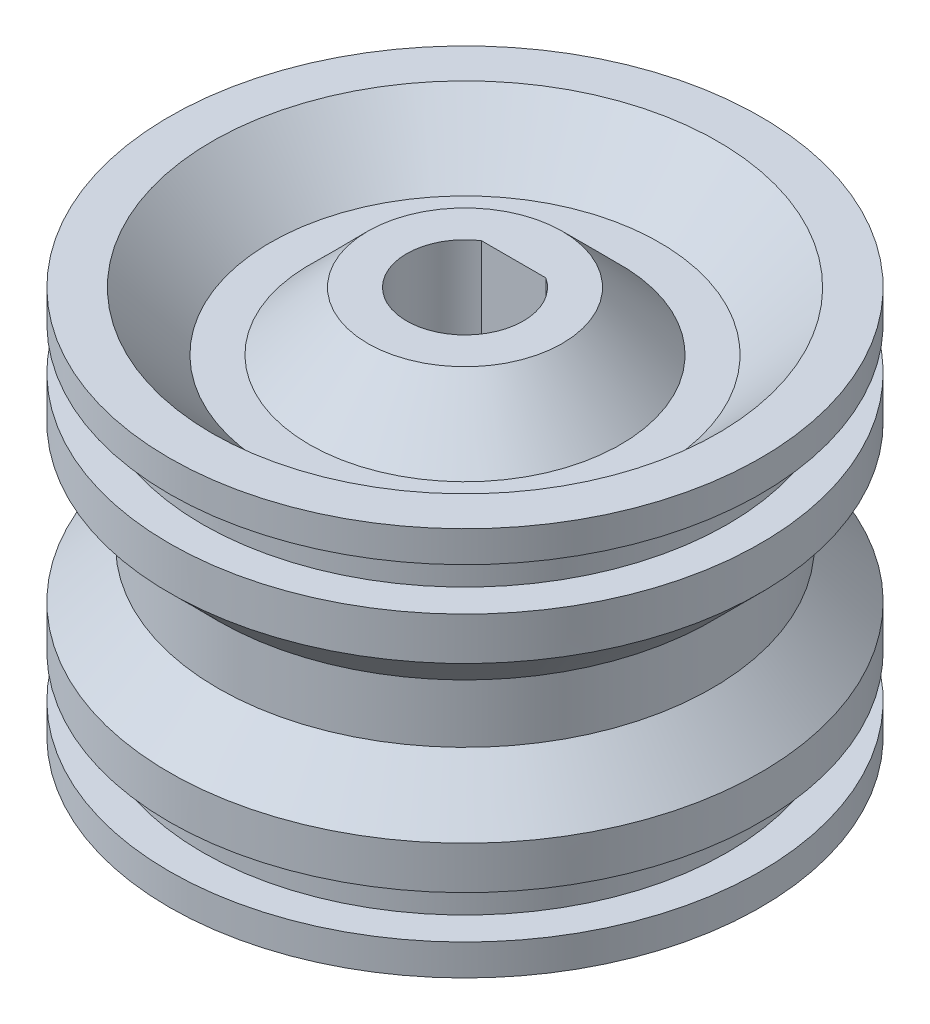
SolidWorks part; units mm, degrees
ref_plane "前视基准面" through (0, 0, 0) normal (0, 0, 1) x (1, 0, 0)
ref_plane "上视基准面" through (0, 0, 0) normal (0, 1, 0) x (1, 0, 0)
ref_plane "右视基准面" through (0, 0, 0) normal (1, 0, 0) x (0, 0, -1)
other "Configuration Table"
sketch "草图1" plane through (0, 0, 0) normal (0, 1, 0) x (1, 0, 0)
  circle A0 centre (0, 0) radius 15.2
  dimension "D1" = 30.4
extrude "凸台-拉伸1" add sketch "草图1" along normal mid plane 20
sketch "草图2" plane through (0, 0, 0) normal (0, 0, 1) x (1, 0, 0)
  line L0 (15.2, -10) -> (15.2, 10) construction
  line L1 (15.2, 8.4) -> (0, 8.4) construction
  line L2 (15.2, 8.4) -> (15.2, 6.2) construction
  line L3 (15.2, 6.2) -> (0, 6.2) construction
  line L4 (0, 8.4) -> (0, 6.2) construction
  line L5 (15.2, 10) -> (-15.2, 10) construction
  line L7 (15.2, 8.4) -> (13.5, 8.4)
  line L8 (15.2, 8.4) -> (15.2, 6.2)
  line L9 (15.2, 6.2) -> (13.5, 6.2)
  line L10 (13.5, 8.4) -> (13.5, 6.2)
  dimension "D1" = 2.2
  dimension "D2" = 1.6
  dimension "D3" = 1.7
revolve "切除-旋转1" cut sketch "草图2" angle 360 about L4
mirror "镜向1" about plane through (0, 0, 0) normal (0, 1, 0) of "切除-旋转1"
sketch "草图4" plane through (0, -10, 0) normal (0, -1, 0) x (1, 0, 0)
  circle A0 centre (0, 0) radius 10
  dimension "D1" = 20
extrude "切除-拉伸1" cut sketch "草图4" against normal blind 12
sketch "草图5" plane through (0, 10, 0) normal (0, 1, 0) x (1, 0, 0)
  line L0 (-1.6583, 2.5) -> (1.6583, 2.5)
  circle A0 centre (0, 0) radius 3
  dimension "D1" = 6
  dimension "D2" = 2.5
extrude "切除-拉伸2" cut sketch "草图5" against normal blind 15 contours L0 A0 region at (0, 10, 0.112)
chamfer "倒角1" distance 3 angle 45 1 edges at (0, -10, -10)
sketch "草图6" plane through (0, 10, 0) normal (0, 1, 0) x (1, 0, 0)
  circle A0 centre (0, 0) radius 5
  circle A1 centre (0, 0) radius 10
  dimension "D1" = 20
  dimension "D2" = 10
extrude "切除-拉伸3" cut sketch "草图6" against normal blind 3
chamfer "倒角2" distance 3 angle 45 2 edges at (0, 7, 5) (0, 10, 10)
sketch "草图7" plane through (0, 0, 0) normal (1, 0, 0) x (0, 0, -1)
  line L0 (15.2, -6.2) -> (15.2, 6.2) construction
  line L1 (12.7, -4) -> (15.2, -4)
  line L2 (12.7, -4) -> (12.7, 4)
  line L3 (12.7, 4) -> (15.2, 4)
  line L4 (15.2, -4) -> (15.2, 4)
  line L5 (12.7, -4) -> (15.2, 4) construction
  line L6 (12.7, 4) -> (15.2, -4) construction
  point P0 (13.95, 0)
  point P7 (0, 0)
  dimension "D1" = 2.5
  dimension "D2" = 8
ref_axis "基准轴1" through (0, 2, 0) along (0, 1, 0)
revolve "切除-旋转2" cut sketch "草图7" angle 360 about axis through (0, 2, 0) along (0, 1, 0)
chamfer "倒角3" distance 2.5 angle 45 2 edges at (0, 4, -12.7) (0, -4, -12.7)
chamfer "倒角4" distance 2 angle 45 1 edges at (0, 2, -10)
